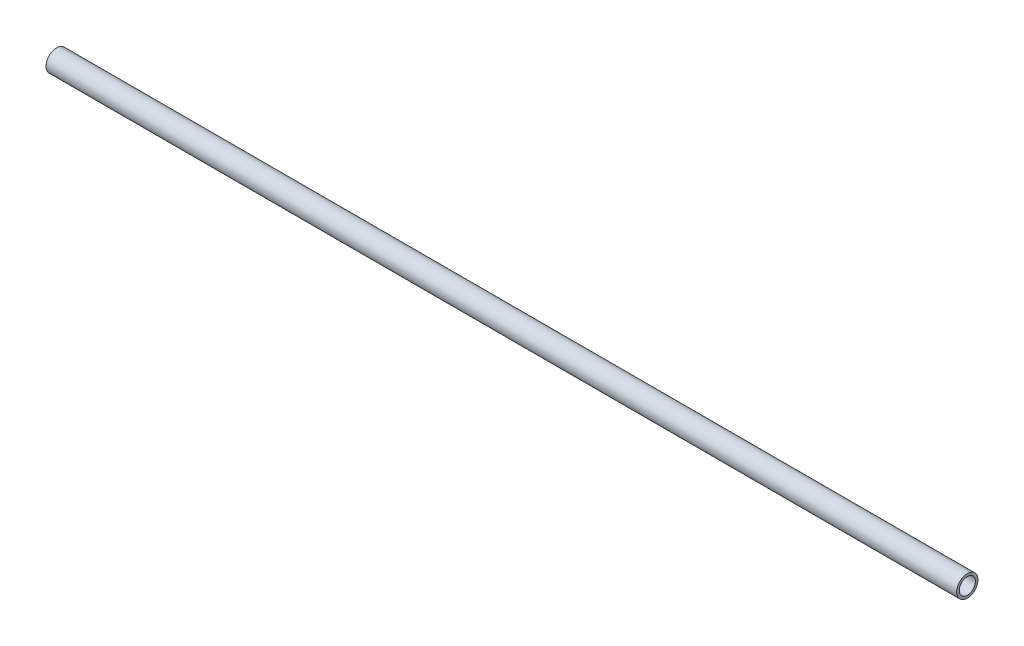
SolidWorks part; units mm, degrees
ref_plane "Front Plane" through (0, 0, 0) normal (0, 0, 1) x (1, 0, 0)
ref_plane "Top Plane" through (0, 0, 0) normal (0, 1, 0) x (1, 0, 0)
ref_plane "Right Plane" through (0, 0, 0) normal (1, 0, 0) x (0, 0, -1)
ref_axis "Axis1" through (-4.5, 0, 0) along (1, 0, 0)
sketch "Sketch1" plane through (0, 0, 0) normal (1, 0, 0) x (0, 0, -1)
  circle A0 centre (0, 0) radius 0.8001
  circle A1 centre (0, 0) radius 1.0541
  dimension "D1" = 1.6002
  dimension "D2" = 2.1082
extrude "Boss-Extrude1" add sketch "Sketch1" along normal blind 90
sketch "Sketch2" plane through (0, 0, 0) normal (-1, 0, 0) x (0, 0, 1)
  line L0 (0, 0) -> (0, 0.6106) construction
  line L2 (-0.304, 0.6106) -> (-0.304, 1.0992)
  line L3 (-0.304, 1.0992) -> (0.304, 1.0992)
  line L4 (0.304, 1.0992) -> (0.304, 0.6106)
  arc A0 (-0.304, 0.6106) -> (0.304, 0.6106) centre (0, 0.6106) ccw
  dimension "D1" = 0.608
extrude "Cut-Extrude1" [suppressed] cut sketch "Sketch2" against normal blind 1
sketch "Sketch3" plane through (0, 0, 0) normal (0, 0, 1) x (1, 0, 0)
  line L0 (1.0797, 0) -> (4.2297, 0) construction
  line L1 (1.0797, 0.7937) -> (4.2297, 0.7937)
  line L2 (1.0797, -0.7937) -> (4.2297, -0.7937)
  arc A0 (1.0797, 0.7937) -> (1.0797, -0.7937) centre (1.0797, 0) ccw
  arc A1 (4.2297, -0.7937) -> (4.2297, 0.7937) centre (4.2297, 0) ccw
  point P3 (2.6547, 0)
  dimension "D1" = 0.7937
  dimension "D2" = 3.15
extrude "Cut-Extrude2" cut sketch "Sketch3" against normal blind 10
equation "\"Do\"=8.5mm"
equation "\"Lo\"=10"
equation "\"screw_diam\" = 3.5mm"
equation "\"wheel_Do\"=12.5mm"
equation "\"wheel_thickness\"=4mm"
equation "\"Collet_diameter\"=4.3"
equation "\"clearance\"= 0.5mm"
equation "\"handle_body_width\" = 10mm"
equation "\"finger_diameter\"=35"
equation "\"collet_lid_diameter\"=10"
equation "\"screw_cap_diam\"=5.15"
equation "\"handle_thickness\"=12.5mm"
equation "\"post_hole_diam\"=2"
equation "\"roll_rod_diam\"= 6.5 "
equation "\"roll_rod_length\"=6.6"
equation "\"disc_diam\"=5"
equation "\"disc_width\"=1.5"
equation "\"arm_width\"=5"
equation "\"arm_thickness\"=4.5"
equation "\"wheel_total_diam\"=30"
equation "\"spring_diam\"=4.1"
equation "\"collet_length\" = 18.75mm"
equation "\"tip_length\" = 40mm"
equation "\"cable_tube_OD\"=0.508"
equation "\"D1@Sketch2\"=\"cable_tube_OD\"+0.1"
